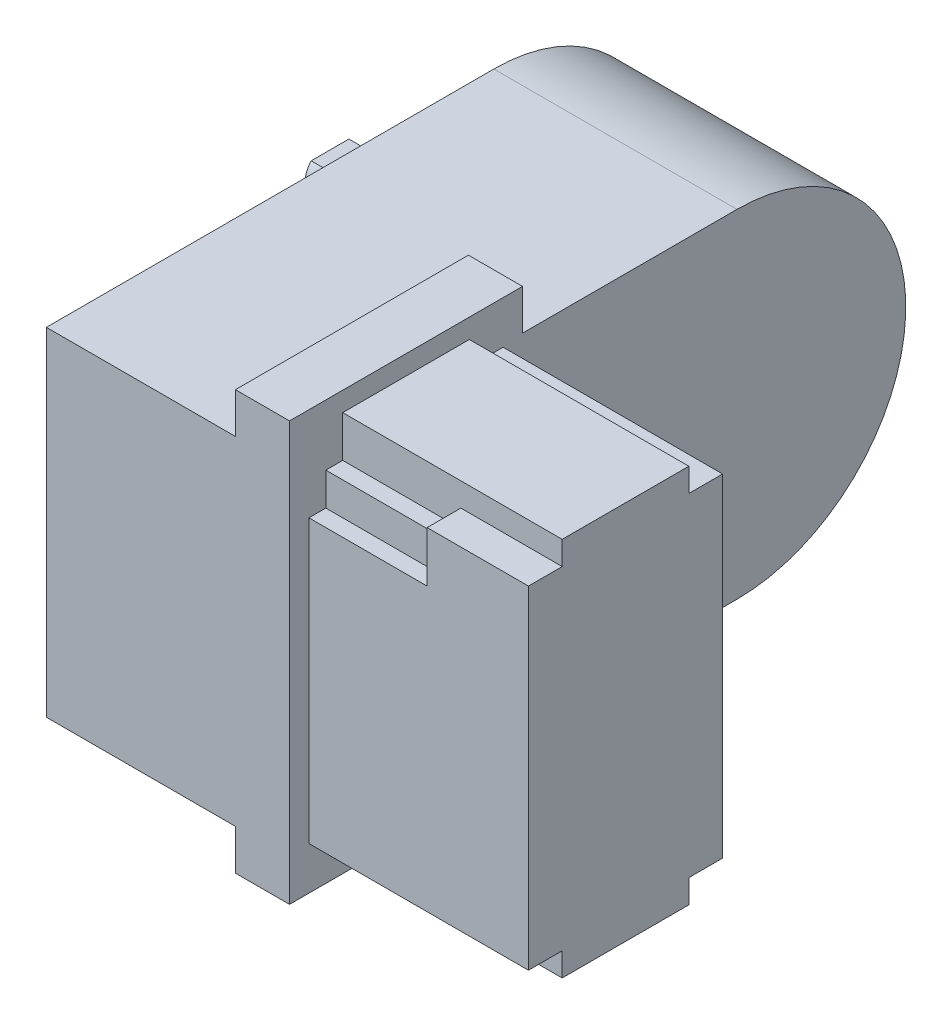
SolidWorks part; units mm, degrees
material "PE Low/Medium Density"
ref_plane "Front Plane" through (0, 0, 0) normal (0, 0, 1) x (1, 0, 0)
ref_plane "Top Plane" through (0, 0, 0) normal (0, 1, 0) x (1, 0, 0)
ref_plane "Right Plane" through (0, 0, 0) normal (1, 0, 0) x (0, 0, -1)
sketch "Sketch1" plane through (0, 0, 0) normal (0, 0, 1) x (1, 0, 0)
  line L0 (-21.1261, 0) -> (52.9977, 0) construction
  line L1 (0, 10) -> (31.5, 10)
  line L2 (0, 10) -> (0, -10)
  line L3 (0, -10) -> (31.5, -10)
  line L4 (31.5, 10) -> (31.5, -10)
  line L5 (31.5, 11.25) -> (44.5, 11.25)
  line L6 (44.5, 11.25) -> (44.5, -11.25)
  line L7 (44.5, -11.25) -> (31.5, -11.25)
  line L9 (31.5, 12.4) -> (28.2955, 12.4)
  line L10 (31.5, 12.4) -> (31.5, -12.4)
  line L11 (31.5, -12.4) -> (28.2955, -12.4)
  line L12 (28.2955, 12.4) -> (28.2955, -12.4)
  circle A0 centre (0, 0) radius 10
  point P11 (-10, 0)
  dimension "D1" = 20
  dimension "D2" = 31.5
  dimension "D3" = 54.5
  dimension "D4" = 22.5
  dimension "D5" = 24.8
extrude "Boss-Extrude1" add sketch "Sketch1" along normal mid plane 13.8 contours L0 A0 L2 | A0 L0 L2 | L2 L0 A0 | L0 L2 A0 | L0 A0 L3 L12 | A0 L0 L12 L1 | L9 L12 L11 L10 region at (-4.2441, 4.2441, 0) region at (-4.2441, -4.2441, 0) region at (4.2441, 4.2441, 0) region at (4.2441, -4.2441, 0) region at (17.9529, 5.2904, 0) region at (17.9529, -5.2904, 0)
extrude "Boss-Extrude2" add sketch "Sketch1<3>" along normal mid plane 11.5 separate body contours L4 L0 L6 L5 L10 | L0 L10 L7 L6 region at (38, 5.625, 0) region at (38, -5.625, 0)
sketch "Sketch1<3>" plane through (0, 0, 0) normal (0, 0, 1) x (1, 0, 0) same geometry as "Sketch1"
sketch "Sketch2" plane through (0, 0, 6.9) normal (0, 0, 1) x (1, 0, 0)
  line L0 (-2.4921, 1) -> (3.6477, 1)
  circle A0 centre (0, 0) radius 1.5
  dimension "D1" = 1
extrude "Boss-Extrude3" add sketch "Sketch2" along normal blind 9.7 contours L0 A0 region at (0, -0.148, 6.9)
sketch "Sketch3" plane through (0, -11.25, 0) normal (0, -1, 0) x (1, 0, 0)
  line L0 (44.5, 5.75) -> (44.5, -5.75) construction
  line L1 (31.5, 5.75) -> (44.5, 5.75)
  line L2 (31.5, 5.75) -> (31.5, 3.75)
  line L3 (31.5, 3.75) -> (44.5, 3.75)
  line L4 (44.5, 5.75) -> (44.5, 3.75)
  line L5 (31.5, 6.9) -> (31.5, -6.9) construction
  line L6 (31.5, -5.75) -> (44.5, -5.75)
  line L7 (31.5, -5.75) -> (31.5, -3.75)
  line L8 (31.5, -3.75) -> (44.5, -3.75)
  line L9 (44.5, -5.75) -> (44.5, -3.75)
  line L10 (44.5, -5.75) -> (31.5, -5.75) construction
  line M1 (31.5, -5.75) -> (44.5, -5.75)
  line M2 (44.5, -5.75) -> (44.5, 5.75)
  line M3 (44.5, 5.75) -> (31.5, 5.75)
  line M4 (31.5, 5.75) -> (31.5, -5.75)
  dimension "D1" = 7.5
  dimension "D2" = 2
extrude "Cut-Extrude1" cut sketch "Sketch3" against normal blind 1.397 contours L3 M4 M2 M3 | L8 M4 M1 M2 region at (38, -11.25, 4.75) region at (38, -11.25, -4.75)
mirror "Mirror1" about plane through (0, 0, 0) normal (0, 1, 0) of "Cut-Extrude1"
sketch "Sketch4" plane through (0, 0, -5.75) normal (0, 0, -1) x (-1, 0, 0)
  line L0 (-38.5, -8.837) -> (-31.5, -8.837)
  line L1 (-31.5, -9.853) -> (-38.5, -9.853)
  line L2 (-31.5, -9.853) -> (-31.5, -6.805)
  line L3 (-31.5, -6.805) -> (-38.5, -6.805)
  line L4 (-38.5, -9.853) -> (-38.5, -6.805)
  line L5 (-31.5, -11.25) -> (-44.5, -11.25) construction
  line M3 (-44.5, -9.853) -> (-31.5, -9.853)
  line M4 (-31.5, -9.853) -> (-31.5, 9.853)
  dimension "D1" = 7
  dimension "D2" = 2.413
  dimension "D3" = 4.445
extrude "Cut-Extrude2" cut sketch "Sketch4" against normal up to surface (2 mm away) contours L4 L0 M3 M4 region at (35, -9.345, -5.75) up to face at (38, -10.5515, -3.75)
sketch "Sketch6" plane through (0, 0, 5.75) normal (0, 0, 1) x (1, 0, 0)
  line L0 (38.5, 8.8) -> (31.5, 8.8)
  line L1 (31.5, 9.853) -> (38.5, 9.853)
  line L2 (31.5, 9.853) -> (31.5, 6.853)
  line L3 (31.5, 6.853) -> (38.5, 6.853)
  line L4 (38.5, 9.853) -> (38.5, 6.853)
  line L5 (31.5, 9.853) -> (44.5, 9.853) construction
  line L6 (31.5, 11.25) -> (44.5, 11.25) construction
  line M2 (44.5, 9.853) -> (31.5, 9.853)
  line M3 (31.5, 9.853) -> (31.5, -9.853)
  dimension "D1" = 3
  dimension "D2" = 7
  dimension "D3" = 2.45
extrude "Cut-Extrude4" cut sketch "Sketch6" against normal blind 1 contours L4 L0 L3 M3 region at (35, 7.8265, 5.75)
extrude "Cut-Extrude3" cut sketch "Sketch4<3>" against normal blind 0.95 contours L4 L0 L3 M4 region at (35, -7.821, -5.75)
sketch "Sketch4<3>" plane through (0, 0, -5.75) normal (0, 0, -1) x (-1, 0, 0) same geometry as "Sketch4"
extrude "Cut-Extrude5" cut sketch "Sketch6<3>" against normal up to surface (2 mm away) contours L4 L0 M2 M3 region at (35, 9.3265, 5.75) up to face at (38, 10.5515, 3.75)
sketch "Sketch6<3>" plane through (0, 0, 5.75) normal (0, 0, 1) x (1, 0, 0) same geometry as "Sketch6"
sketch "Sketch8" plane through (0, 0, 0) normal (0, 0, 1) x (1, 0, 0)
  line L0 (28.2955, 11.9) -> (26.7955, 10.4)
  line L1 (28.2955, 12.4) -> (28.2955, 10) construction
  line L2 (26.7955, 10.4) -> (28.2955, 10.4)
  line L3 (28.2955, 10.4) -> (28.2955, 11.9)
  line L4 (28.2955, 11.9) -> (28.2984, 11.8779)
  line L5 (31.5, 12.4) -> (28.2955, 12.4) construction
  line L6 (28.2955, -10.4) -> (28.2955, -11.9)
  line L7 (28.2955, -10) -> (28.2955, -12.4) construction
  line L8 (28.2955, -11.9) -> (26.7955, -10.4)
  line L9 (26.7955, -10.4) -> (28.2955, -10.4)
  line L10 (31.5, -12.4) -> (28.2955, -12.4) construction
  dimension "D1" = 2
  dimension "D2" = 0.5
  dimension "D3" = 1.5
  dimension "D4" = 0.5
  dimension "D5" = 2
  dimension "D6" = 1.5
extrude "Boss-Extrude4" add sketch "Sketch8" along normal up to surface (3.75 mm away) and the other way up to surface (3.75 mm away) contours L2 L3 L0 | L9 L8 L6 region at (27.7955, 10.9, 0) region at (27.7955, -10.9, 0) up to face at (38.1667, 9.9677, 3.75) other way up to face at (38, 10.5515, -3.75)
sketch "Sketch9" plane through (0, 10, 0) normal (0, 1, 0) x (1, 0, 0)
  line L0 (44.5, -3.75) -> (44.5, 3.75) construction
  line L1 (17.1, 12.7862) -> (-19.4852, 12.7862)
  line L2 (17.1, 12.7862) -> (17.1, -19.9479)
  line L3 (17.1, -19.9479) -> (-19.4852, -19.9479)
  line L4 (-19.4852, 12.7862) -> (-19.4852, -19.9479)
  dimension "D1" = 27.4
  dimension "D2" = 36.5852
  dimension "D3" = 32.7342
extrude "Cut-Extrude6" cut sketch "Sketch9" against normal through all
sketch "Sketch10" plane through (17.1, 0, 0) normal (-1, 0, 0) x (0, 0, 1)
  line L0 (-19.6, 10) -> (6.9, 10)
  line L1 (6.9, 10) -> (6.9, -10)
  line L2 (6.9, -10) -> (-19.6, -10)
  circle A0 centre (-19.6, 0) radius 10
  point P5 (-29.6, 0)
  line M3 (-6.9, 10) -> (-6.9, -10)
  dimension "D1" = 36.5
extrude "Boss-Extrude5" add sketch "Sketch10" against normal up to surface (14.4 mm away) contours A0 | A0 L2 L0 M3 region at (17.1, 9.7631, -13.25) region at (17.1, 0, -19.6) up to face at (31.5, 0, 0)
sketch "Sketch11" plane through (17.1, 0, 0) normal (-1, 0, 0) x (0, 0, 1)
  line L0 (-23.3958, 1) -> (-14.4274, 1)
  circle A0 centre (-19.6, 0) radius 1.5
  dimension "D1" = 1
extrude "Boss-Extrude6" add sketch "Sketch11" along normal blind 9.7 contours L0 A0 region at (17.1, -0.148, -19.6)
